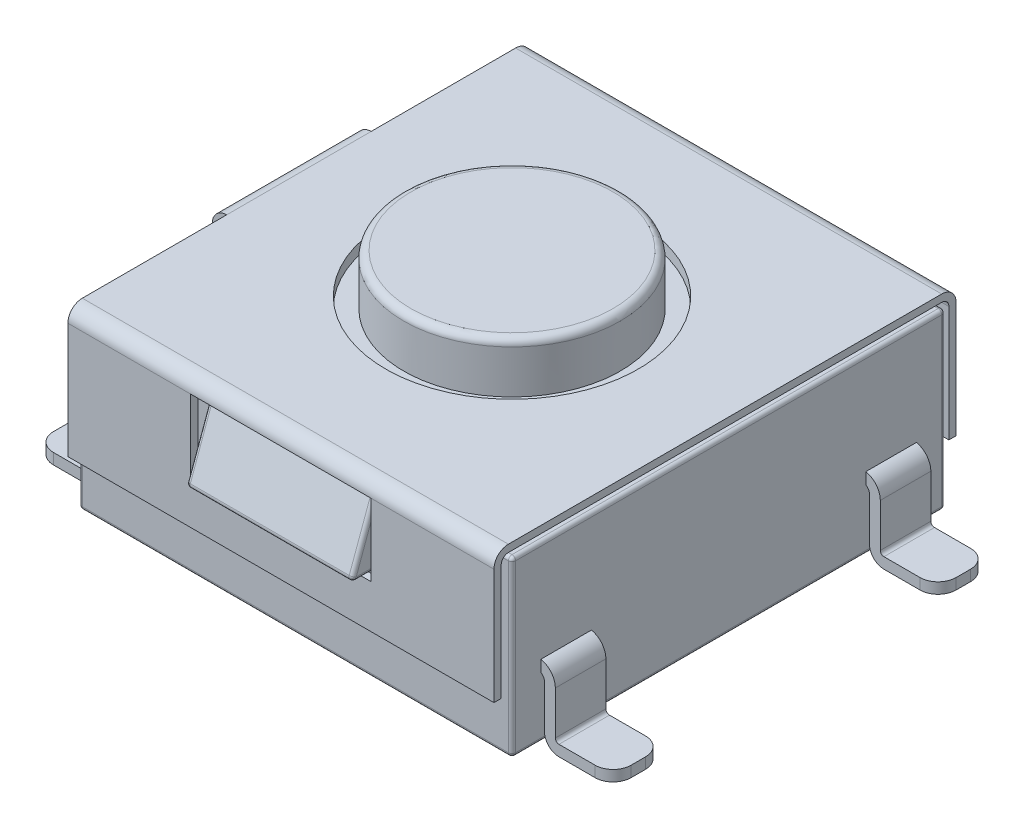
SolidWorks part; units mm, degrees
ref_plane "Front Plane" through (0, 0, 0) normal (0, 0, 1) x (1, 0, 0)
ref_plane "Top Plane" through (0, 0, 0) normal (0, 1, 0) x (1, 0, 0)
ref_plane "Right Plane" through (0, 0, 0) normal (1, 0, 0) x (0, 0, -1)
sketch "Sketch1" plane through (0, 0, 0) normal (0, 1, 0) x (1, 0, 0)
  line L1 (-3, -3) -> (3, -3)
  line L2 (-3, -3) -> (-3, 3)
  line L3 (-3, 3) -> (3, 3)
  line L4 (3, -3) -> (3, 3)
  line L5 (-3, -3) -> (3, 3) construction
  line L6 (-3, 3) -> (3, -3) construction
  point P0 (0, 0)
  dimension "D1" = 6
  dimension "D2" = 6
extrude "Boss-Extrude1" add sketch "Sketch1" along normal blind 2.4
sketch "Sketch2" plane through (0, 0, 0) normal (0, 0, 1) x (1, 0, 0)
  line L0 (-4, -0.05) -> (-3.25, -0.05)
  line L1 (-3.05, 0.15) -> (-3.05, 2.35)
  line L2 (-2.95, 2.45) -> (2.95, 2.45)
  line L3 (3.05, 2.35) -> (3.05, 0.15)
  line L4 (3.25, -0.05) -> (4, -0.05)
  line L5 (-3, 2.4) -> (-3, 0) construction
  line L6 (3, 2.4) -> (3, 0) construction
  line L7 (-3, 2.4) -> (3, 2.4) construction
  line L8 (-4, 0.05) -> (-3.25, 0.05)
  line L9 (-3.15, 0.15) -> (-3.15, 2.35)
  line L10 (-2.95, 2.55) -> (2.95, 2.55)
  line L11 (3.15, 2.35) -> (3.15, 0.15)
  line L12 (3.25, 0.05) -> (4, 0.05)
  line L13 (-4, 0.05) -> (-4, -0.05)
  line L14 (4, 0.05) -> (4, -0.05)
  arc A0 (2.95, 2.45) -> (3.05, 2.35) centre (2.95, 2.35) cw
  arc A1 (-3.05, 2.35) -> (-2.95, 2.45) centre (-2.95, 2.35) cw
  arc A2 (3.05, 0.15) -> (3.25, -0.05) centre (3.25, 0.15) ccw
  arc A3 (-3.25, -0.05) -> (-3.05, 0.15) centre (-3.25, 0.15) ccw
  arc A4 (-3.25, 0.05) -> (-3.15, 0.15) centre (-3.25, 0.15) ccw
  arc A5 (-3.15, 2.35) -> (-2.95, 2.55) centre (-2.95, 2.35) cw
  arc A6 (2.95, 2.55) -> (3.15, 2.35) centre (2.95, 2.35) cw
  arc A7 (3.15, 0.15) -> (3.25, 0.05) centre (3.25, 0.15) ccw
  dimension "D4" = 0.1
  dimension "D5" = 0.2
  dimension "D1" = 0.05
  dimension "D2" = 0.05
  dimension "D3" = 0.05
  dimension "D6" = 2.5
  dimension "D8" = 8
  dimension "D7" = 0.1
extrude "Boss-Extrude2" add sketch "Sketch2" along normal mid plane 6 separate body
sketch "Sketch3" plane through (0, 2.55, 0) normal (0, 1, 0) x (1, 0, 0)
  circle A0 centre (0, 0) radius 1.75
  dimension "D1" = 3.5
extrude "Cut-Extrude1" cut sketch "Sketch3" against normal blind 0.1
sketch "Sketch12" plane through (0, 2.55, 0) normal (0, 1, 0) x (1, 0, 0)
  circle A0 centre (0, 0) radius 1.75 construction
  circle A1 centre (0, 0) radius 1.75
  circle A2 centre (0, 0) radius 1.85
  dimension "D1" = 0.1
extrude "Boss-Extrude7" add sketch "Sketch12" against normal up to surface (0.15 mm away) up to face at (0, 2.4, 0)
sketch "Sketch4" plane through (0, 2.4, 0) normal (0, 1, 0) x (1, 0, 0)
  circle A0 centre (0, 0) radius 1.5
  circle A1 centre (0, 0) radius 1.75 construction
  dimension "D1" = 3
extrude "Boss-Extrude3" add sketch "Sketch4" along normal blind 0.7
fillet "Fillet1" radius 0.1 1 edges at (0, 3.1, 1.5)
sketch "Sketch7" plane through (0, 0, 3) normal (0, 0, 1) x (1, 0, 0)
  line L6 (2.95, 2.55) -> (2.95, 2.45)
  line L14 (-4, 0.05) -> (-4, -0.05)
  line L15 (-2.95, 2.45) -> (2.95, 2.45)
  line L16 (3.05, 2.35) -> (3.05, 0.15)
  line L17 (3.25, -0.05) -> (4, -0.05)
  line L18 (4, -0.05) -> (4, 0.05)
  line L19 (4, 0.05) -> (3.25, 0.05)
  line L20 (3.15, 0.15) -> (3.15, 2.35)
  line L21 (2.95, 2.55) -> (-2.95, 2.55)
  line L24 (3.05, 2.35) -> (3.05, 0.15)
  line L25 (3.25, -0.05) -> (4, -0.05)
  line L26 (4, -0.05) -> (4, 0.05)
  line L27 (4, 0.05) -> (3.25, 0.05)
  line L28 (3.15, 0.15) -> (3.15, 2.35)
  line L33 (-4, -0.05) -> (-3.25, -0.05)
  line L35 (-3.05, 0.15) -> (-3.05, 2.35)
  line L37 (-3.15, 2.35) -> (-3.15, 0.15)
  line L39 (-3.25, 0.05) -> (-4, 0.05)
  arc A8 (3.05, 2.35) -> (2.95, 2.45) centre (2.95, 2.35) ccw
  arc A9 (3.05, 0.15) -> (3.25, -0.05) centre (3.25, 0.15) ccw
  arc A10 (3.15, 0.15) -> (3.25, 0.05) centre (3.25, 0.15) ccw
  arc A11 (3.15, 2.35) -> (2.95, 2.55) centre (2.95, 2.35) ccw
  arc A12 (3.05, 2.35) -> (2.95, 2.45) centre (2.95, 2.35) ccw
  arc A13 (3.05, 0.15) -> (3.25, -0.05) centre (3.25, 0.15) ccw
  arc A14 (3.15, 0.15) -> (3.25, 0.05) centre (3.25, 0.15) ccw
  arc A15 (3.15, 2.35) -> (2.95, 2.55) centre (2.95, 2.35) ccw
  arc A20 (-3.25, -0.05) -> (-3.05, 0.15) centre (-3.25, 0.15) ccw
  arc A22 (-2.95, 2.45) -> (-3.05, 2.35) centre (-2.95, 2.35) ccw
  arc A24 (-2.95, 2.55) -> (-3.15, 2.35) centre (-2.95, 2.35) ccw
  arc A26 (-3.25, 0.05) -> (-3.15, 0.15) centre (-3.25, 0.15) ccw
  dimension "D1" = 0
extrude "Cut-Extrude4" cut sketch "Sketch7" against normal through all
sketch "Sketch6" plane through (0, 0, 3) normal (0, 0, 1) x (1, 0, 0)
  line L0 (-2.95, 2.45) -> (-2.95, 2.55)
  line L10 (2.95, 2.45) -> (2.95, 2.55)
  line L12 (-4, 0.05) -> (-4, -0.05)
  line L13 (-4, -0.05) -> (-3.25, -0.05)
  line L14 (-3.05, 0.15) -> (-3.05, 2.35)
  line L15 (-2.95, 2.45) -> (2.95, 2.45)
  line L21 (2.95, 2.55) -> (-2.95, 2.55)
  line L22 (-3.15, 2.35) -> (-3.15, 0.15)
  line L23 (-3.25, 0.05) -> (-4, 0.05)
  line L24 (-4, 0.05) -> (-4, -0.05)
  line L25 (-4, -0.05) -> (-3.25, -0.05)
  line L26 (-3.05, 0.15) -> (-3.05, 2.35)
  line L34 (-3.15, 2.35) -> (-3.15, 0.15)
  line L35 (-3.25, 0.05) -> (-4, 0.05)
  arc A8 (-3.25, -0.05) -> (-3.05, 0.15) centre (-3.25, 0.15) ccw
  arc A9 (-2.95, 2.45) -> (-3.05, 2.35) centre (-2.95, 2.35) ccw
  arc A14 (-2.95, 2.55) -> (-3.15, 2.35) centre (-2.95, 2.35) ccw
  arc A15 (-3.25, 0.05) -> (-3.15, 0.15) centre (-3.25, 0.15) ccw
  arc A16 (-3.25, -0.05) -> (-3.05, 0.15) centre (-3.25, 0.15) ccw
  arc A17 (-2.95, 2.45) -> (-3.05, 2.35) centre (-2.95, 2.35) ccw
  arc A22 (-2.95, 2.55) -> (-3.15, 2.35) centre (-2.95, 2.35) ccw
  arc A23 (-3.25, 0.05) -> (-3.15, 0.15) centre (-3.25, 0.15) ccw
  dimension "D1" = 0
extrude "Cut-Extrude3" cut sketch "Sketch6" against normal blind 2
sketch "Sketch5" plane through (-3.05, 0, 0) normal (1, 0, 0) x (0, 0, -1)
  line L1 (-1, -0.05) -> (3, -0.05) construction
  line L2 (-0.35, -0.05) -> (-1, -0.05)
  line L3 (-0.35, -0.05) -> (-0.35, 0.75)
  line L4 (-0.55, 0.95) -> (-1, 0.95)
  line L5 (-1, -0.05) -> (-1, 0.95)
  line L6 (-1, 2.35) -> (-1, 0.15) construction
  arc A0 (-0.35, 0.75) -> (-0.55, 0.95) centre (-0.55, 0.75) ccw
  dimension "D3" = 0.2
  dimension "D1" = 0.35
  dimension "D2" = 1
extrude "Cut-Extrude2" cut sketch "Sketch5" against normal through all
ref_plane "Plane1" through (0, 0, 2.25) normal (0, 0, 1) x (1, 0, 0)
sketch "Sketch11" plane through (0, 0, 2.25) normal (0, 0, 1) x (1, 0, 0)
  line L0 (-4, -0.05) -> (-3.25, -0.05)
  line L1 (-3.05, 0.15) -> (-3.05, 0.75)
  line L2 (-3.05, 0.75) -> (-3.05, 0.95) construction
  line L3 (-2.95, 0.85) -> (2.95, 0.85)
  line L4 (3.05, 0.75) -> (3.05, 0.15)
  line L5 (3.25, -0.05) -> (4, -0.05)
  line L9 (-4, 0.1) -> (-3.25, 0.1)
  line L10 (-3.2, 0.15) -> (-3.2, 0.75)
  line L11 (-2.95, 1) -> (2.95, 1)
  line L12 (3.2, 0.75) -> (3.2, 0.15)
  line L13 (3.25, 0.1) -> (4, 0.1)
  line L14 (4, 0.1) -> (4, -0.05)
  line L15 (-4, 0.1) -> (-4, -0.05)
  arc A0 (3.05, 0.15) -> (3.25, -0.05) centre (3.25, 0.15) ccw
  arc A1 (-3.25, -0.05) -> (-3.05, 0.15) centre (-3.25, 0.15) ccw
  arc A2 (-3.05, 0.75) -> (-2.95, 0.85) centre (-2.95, 0.75) cw
  arc A3 (2.95, 0.85) -> (3.05, 0.75) centre (2.95, 0.75) cw
  arc A4 (-3.25, 0.1) -> (-3.2, 0.15) centre (-3.25, 0.15) ccw
  arc A5 (-3.2, 0.75) -> (-2.95, 1) centre (-2.95, 0.75) cw
  arc A6 (2.95, 1) -> (3.2, 0.75) centre (2.95, 0.75) cw
  arc A7 (3.2, 0.15) -> (3.25, 0.1) centre (3.25, 0.15) ccw
  point P16 (-3.05, 0.85)
  dimension "D3" = 0.2
  dimension "D4" = 0.1
  dimension "D1" = 8
  dimension "D5" = 0.15
extrude "Boss-Extrude6" add sketch "Sketch11" along normal mid plane 0.7
fillet "Fillet2" radius 0.25 6 edges at (-3.1, 0.95, 1) (-4, 0, 0.35) (4, 0.025, 1.9) (4, 0.025, 2.6) (-4, 0.025, 1.9) (-4, 0.025, 2.6)
mirror "Mirror1" about plane through (0, 0, 0) normal (0, 0, 1) of "Fillet2", "Boss-Extrude6", "Cut-Extrude2", "Cut-Extrude3"
sketch "Sketch8" plane through (0, 0, 0) normal (1, 0, 0) x (0, 0, -1)
  line L0 (3.1, 2.35) -> (3.1, 0.75)
  line L1 (3.1, 0.75) -> (3.2, 0.75)
  line L2 (3.2, 0.75) -> (3.2, 2.35)
  line L3 (3, 2.55) -> (3, 2.45)
  line L6 (0, 2.45) -> (0, 0) construction
  line L7 (-3, 2.55) -> (3, 2.55) construction
  line L8 (-3, 2.45) -> (3, 2.45) construction
  line L9 (3, 2.55) -> (3, 2.45) construction
  line L10 (-3, 2.55) -> (-3, 2.45)
  line L11 (-3.2, 0.75) -> (-3.2, 2.35)
  line L12 (-3.1, 0.75) -> (-3.2, 0.75)
  line L13 (-3.1, 2.35) -> (-3.1, 0.75)
  arc A0 (3, 2.45) -> (3.1, 2.35) centre (3, 2.35) cw
  arc A1 (3, 2.55) -> (3.2, 2.35) centre (3, 2.35) cw
  arc A2 (-3, 2.55) -> (-3.2, 2.35) centre (-3, 2.35) ccw
  arc A3 (-3, 2.45) -> (-3.1, 2.35) centre (-3, 2.35) ccw
  dimension "D1" = 0.1
  dimension "D2" = 1.8
extrude "Boss-Extrude4" add sketch "Sketch8" against normal up to surface and the other way up to surface up to face at (-2.95, 2.5, -2) other way up to face at (2.95, 2.5, 0)
sketch "Sketch9" plane through (0, 0, 3.2) normal (0, 0, 1) x (1, 0, 0)
  line L1 (-1.25, 1.35) -> (1.25, 1.35)
  line L2 (-1.25, 1.35) -> (-1.25, 2.35)
  line L3 (-1.25, 2.35) -> (1.25, 2.35)
  line L4 (1.25, 1.35) -> (1.25, 2.35)
  line L5 (-1.25, 1.35) -> (1.25, 2.35) construction
  line L6 (-1.25, 2.35) -> (1.25, 1.35) construction
  line L7 (-2.95, 2.35) -> (2.95, 2.35) construction
  point P0 (0, 1.85)
  dimension "D1" = 2.5
  dimension "D2" = 1
extrude "Cut-Extrude5" cut sketch "Sketch9" against normal blind 0.1
mirror "Mirror2" about plane through (0, 0, 0) normal (0, 0, 1) of "Cut-Extrude5"
sketch "Sketch10" plane through (0, 0, 0) normal (1, 0, 0) x (0, 0, -1)
  line L0 (3, 2.4) -> (3.3785, 1.36)
  line L1 (3, 2.4) -> (3, 0) construction
  line L2 (3.3785, 1.36) -> (3, 1.36)
  line L3 (3, 1.36) -> (3, 2.4)
  line L5 (0, 0) -> (0, 2.4) construction
  line L7 (-3, 1.36) -> (-3, 2.4)
  line L8 (-3.3785, 1.36) -> (-3, 1.36)
  line L9 (-3, 2.4) -> (-3.3785, 1.36)
  line L10 (3.1, 1.35) -> (3.2, 1.35) construction
  line L11 (-3, 2.4) -> (3, 2.4) construction
  dimension "D2" = 0.01
  dimension "D3" = 20
extrude "Boss-Extrude5" add sketch "Sketch10" along normal mid plane 2.3
fillet "Fillet4" radius 0.05 20 edges at (0, 1.36, 3.3785) (0, 1.36, -3.3785) (-3, 1.2, 3) (-3, 2.4, 0) (3, 1.2, -3) (3, 2.4, 0) (3, 1.2, 3) (3, 0, 0) (0, 0, 3) (-3, 0, 0) (0, 0, -3) (-3, 1.2, -3) (-1.15, 1.36, -3.1893) (1.15, 1.36, -3.1893) (-1.15, 1.36, 3.1893) (1.15, 1.36, 3.1893)
fillet "Fillet5" radius 0.05 8 edges at (-2.9854, 2.3854, -2.9854) (2.9854, 2.3854, -2.9854) (2.9854, 2.3854, 2.9854) (-2.9854, 2.3854, 2.9854)
